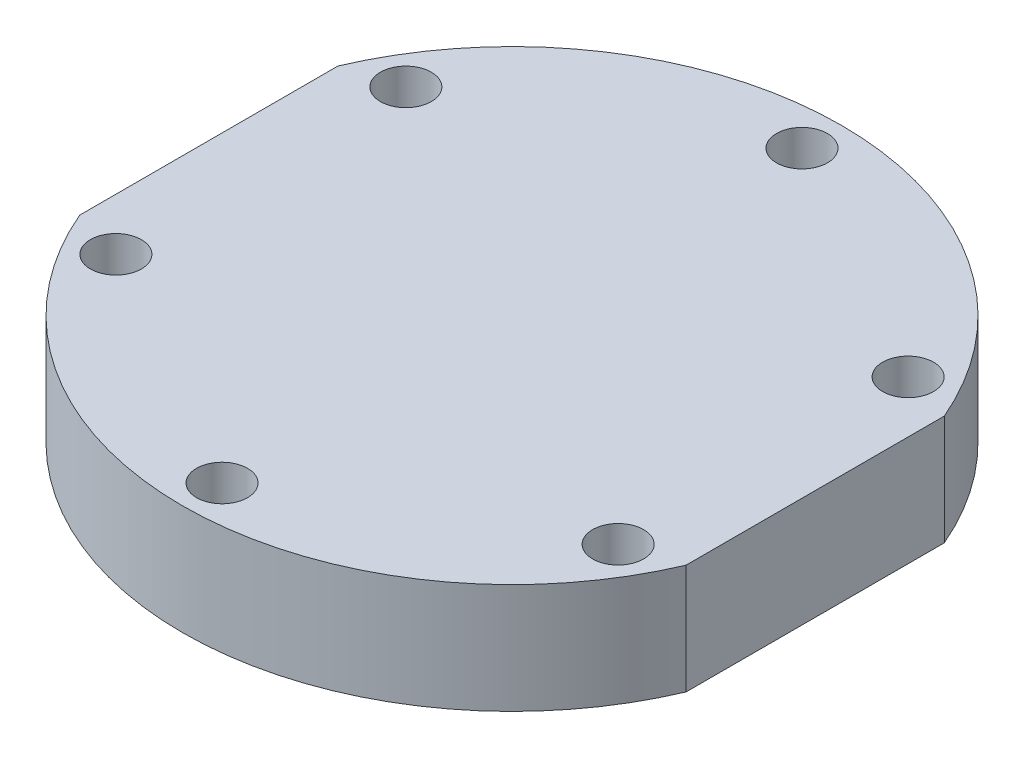
SolidWorks part; units mm, degrees
material "Copper"
ref_plane "Front Plane" through (0, 0, 0) normal (0, 0, 1) x (1, 0, 0)
ref_plane "Top Plane" through (0, 0, 0) normal (0, 1, 0) x (1, 0, 0)
ref_plane "Right Plane" through (0, 0, 0) normal (1, 0, 0) x (0, 0, -1)
ref_axis "Y Axis" through (0, 6.6675, 0) along (0, -1, 0)
sketch "outer" plane through (0, 0, 0) normal (0, 1, 0) x (1, 0, 0)
  circle A0 centre (0, 0) radius 19.05
  dimension "D1" = 38.1
extrude "Body" add sketch "outer" along normal blind 6.35
sketch "inner" plane through (0, 0, 0) normal (0, 1, 0) x (1, 0, 0)
  circle A0 centre (0, 0) radius 11.938
  dimension "D1" = 23.876
extrude "Pocket" cut sketch "inner" along normal blind 3.81
sketch "Screw Position" plane through (0, 0, 0) normal (0, 1, 0) x (1, 0, 0)
  point P0 (0, 16.764)
  dimension "D1" = 16.764
hole_wizard "#4 Clearance Hole1" positions "Sketch7" profile "Sketch8" hole size "#4" standard "ANSI Inch" end condition through all
sketch "Sketch7" plane through (0, 6.35, 0) normal (0, 1, 0) x (1, 0, 0)
  point P0 (0, 16.764)
sketch "Sketch8" plane through (0, 6.35, -16.764) normal (1, 0, 0) x (0, 0, 1)
  line L0 (0, 0) -> (0, 6.35)
  line L1 (0, 6.35) -> (1.4732, 6.35)
  line L2 (1.4732, 6.35) -> (1.4732, 0)
  line L5 (1.4732, 0) -> (0, 0)
  line L11 (0, -6.35) -> (0, 107.95) construction
  dimension "Thru Hole Dia." = 2.9464
  dimension "Thru Hole Depth" = 6.35
pattern_circular "Screw Holes" count 6 over 360 about axis through (0, 6.6675, 0) along (0, -1, 0) of "#4 Clearance Hole1"
sketch "Post Sketch" plane through (0, 0, 0) normal (0, 1, 0) x (1, 0, 0)
  circle A1 centre (3.81, 5.842) radius 2.413
  point P0 (3.81, 8.2543)
  dimension "D1" = 3.81
  dimension "D4" = 4.826
  dimension "D2" = 5.842
extrude "Post" add sketch "Post Sketch" against normal blind 4.572 from surface starting at face at (0, 3.81, 11.938)
pattern_circular "Posts" count 4 over 360 about axis through (0, 6.6675, 0) along (0, -1, 0) of "Post"
sketch "Cut Sketch" plane through (0, 0, 0) normal (0, 1, 0) x (1, 0, 0)
  line L0 (-17.526, -19.05) -> (-20.574, -19.05)
  line L1 (17.526, 19.05) -> (20.574, 19.05)
  line L2 (17.526, 19.05) -> (17.526, -19.05)
  line L3 (17.526, -19.05) -> (20.574, -19.05)
  line L4 (20.574, 19.05) -> (20.574, -19.05)
  line L5 (17.526, 19.05) -> (20.574, -19.05) construction
  line L6 (17.526, -19.05) -> (20.574, 19.05) construction
  line L7 (-17.526, -19.05) -> (-17.526, 19.05)
  line L8 (-17.526, 19.05) -> (-20.574, 19.05)
  line L9 (-20.574, -19.05) -> (-20.574, 19.05)
  line L10 (-17.526, -19.05) -> (-20.574, 19.05) construction
  line L11 (-17.526, 19.05) -> (-20.574, -19.05) construction
  circle A0 centre (0, 0) radius 19.05 construction
  point P0 (19.05, 0)
  point P9 (-19.05, 0)
  point P14 (0, 0)
  dimension "D1" = 38.1
  dimension "D2" = 3.048
  dimension "D3" = 2
extrude "Flat Cut" cut sketch "Cut Sketch" against normal through all and the other way through all
equation "\"outer_d\"= 3 / 2in"
equation "\"top_h\"= 1 / 4in"
equation "\"screw_r\"= 0.66in"
equation "\"inner_d\"= 0.94in"
equation "\"inner_h\"= 150mil"
equation "\"D1@outer\" = \"outer_d\""
equation "\"D1@Body\" = \"top_h\""
equation "\"D1@inner\"=\"inner_d\""
equation "\"D1@Pocket\" = \"inner_h\""
equation "\"D1@Screw Position\"=\"screw_r\""
equation "\"post_x\" = 0.15in"
equation "\"post_z\"= 0.23in"
equation "\"post_bottom_h\"= 0.03in"
equation "\"post_size\" = 0.190in"
equation "\"D1@Post\" = \"inner_h\" + \"post_bottom_h\""
equation "\"cut\"= 0.06in"
equation "\"D1@Cut Sketch\"=\"outer_d\""
equation "\"D2@Cut Sketch\"=2 * \"cut\""
equation "\"D1@Post Sketch\"=\"post_x\""
equation "\"D4@Post Sketch\"=\"post_size\""
equation "\"D2@Post Sketch\"=\"post_z\""
